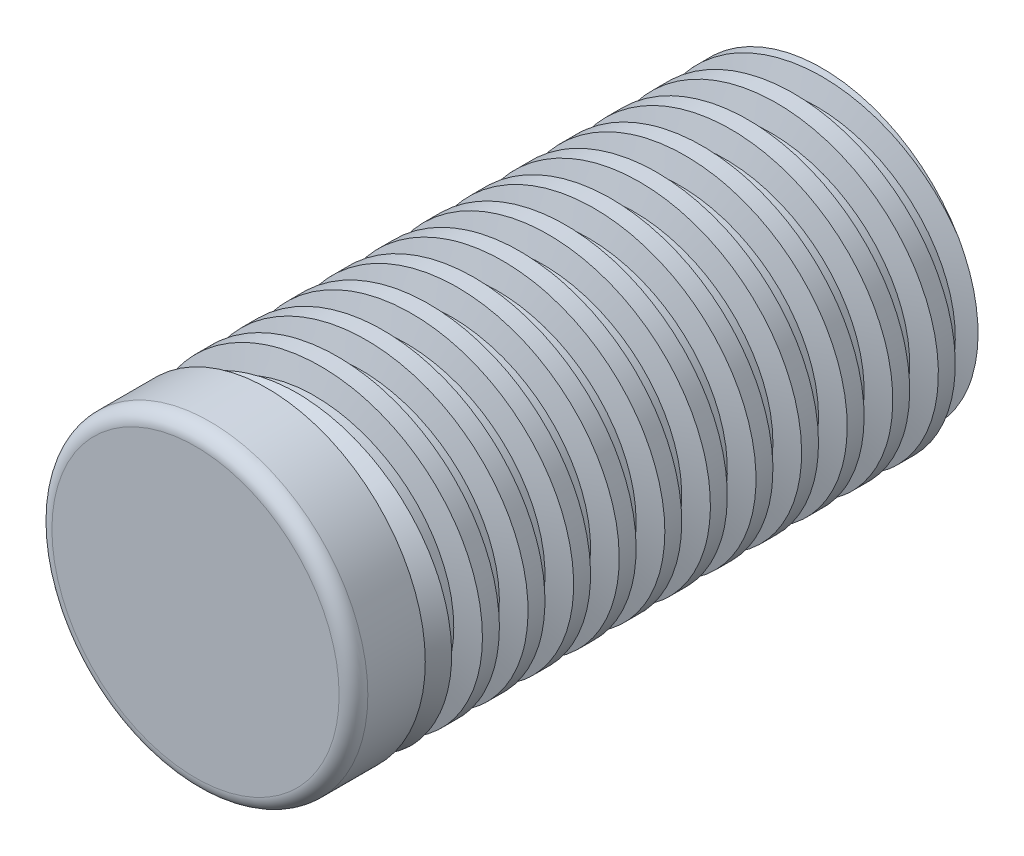
SolidWorks part; units mm, degrees
ref_plane "Front" through (0, 0, 0) normal (0, 0, 1) x (1, 0, 0)
ref_plane "Top" through (0, 0, 0) normal (0, 1, 0) x (1, 0, 0)
ref_plane "Right" through (0, 0, 0) normal (1, 0, 0) x (0, 0, -1)
sketch "Sketch1" plane through (0, 0, 0) normal (0, 0, 1) x (1, 0, 0)
  circle A0 centre (0, 0) radius 11
  dimension "ThreadDia" = 22
extrude "Boss-Extrude1" add sketch "Sketch1" along normal mid plane 40
sketch "Sketch2" plane through (0, 0, 20) normal (0, 0, 1) x (1, 0, 0)
  circle A1 centre (0, 0) radius 11
  circle A2 centre (0, 0) radius 11
  dimension "D1" = 0
curve "Helix/Spiral1" pitch 3.175 height 43.175 turns 13.5984 parameters "Pitch"=3.175
sketch "Sketch3" plane through (0, 0, 0) normal (1, 0, 0) x (0, 0, -1)
  line L0 (-20, 11) -> (-20.4105, 9.4126)
  line L1 (-20.4105, 9.4126) -> (-21.5875, 9.4126)
  line L2 (-21.5875, 9.4126) -> (-21.998, 11)
  line L3 (-21.998, 11) -> (-20, 11)
  line L4 (-21.7928, 10.2063) -> (-20.2053, 10.2063) construction
  line L5 (-20.999, 10.2063) -> (-20.999, 9.4126) construction
  dimension "D1" = 29
  dimension "D2" = 1.177
  dimension "D3" = 1.5875
chamfer "Chamfer1" distance 2.3813 angle 30 2 edges at (11, 0, -20) (11, 0, 20) first distance on face at (11, 0, -20) first distance on face at (11, 0, 20)
sweep "Cut-Sweep1" cut profiles "Sketch3" path "Helix/Spiral1"
sketch "Sketch4" plane through (0, 0, -20) normal (0, 0, -1) x (-1, 0, 0)
  circle A0 centre (0, 0) radius 11
  dimension "D1" = 22
sketch "Sketch5" plane through (0, 0, 20) normal (0, 0, 1) x (1, 0, 0)
  circle A0 centre (0, 0) radius 11
  dimension "D1" = 22
extrude "Boss-Extrude3" add sketch "Sketch5" along normal blind 5
fillet "Fillet1" radius 1 1 edges at (11, 0, 25) type face fillet first side face at (11, 0, 25) second side face at (11, 0, 25)
equation "\"D3@Helix/Spiral1\" = \"Length@Boss-Extrude1\"+\"Pitch@Helix/Spiral1\""
equation "\"D2@Sketch3\" = \"Pitch@Helix/Spiral1\"*.3707"
equation "\"D3@Sketch3\" = \"Pitch@Helix/Spiral1\"*.5"
equation "\"D1@Chamfer1\" = \"Pitch@Helix/Spiral1\"*.75"
